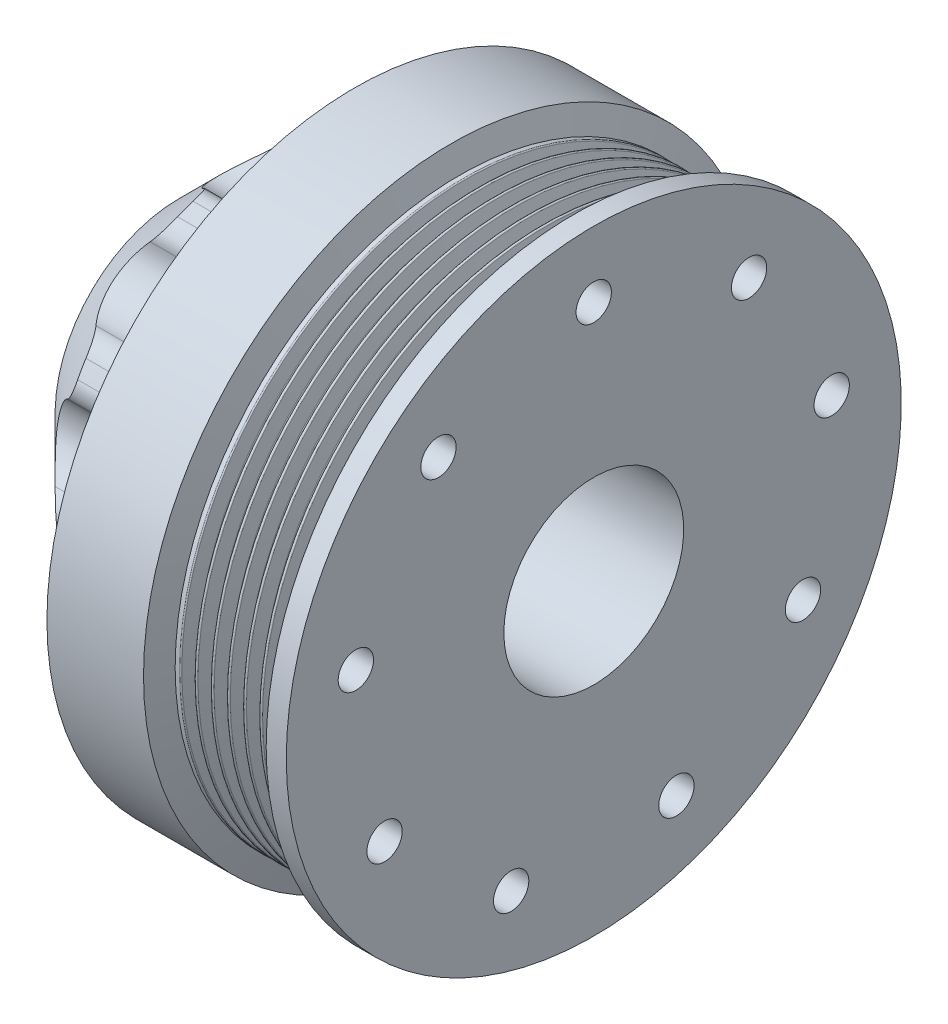
SolidWorks part; units mm, degrees
material "6061-T6 (SS)"
ref_plane "Front Plane" through (0, 0, 0) normal (0, 0, 1) x (1, 0, 0)
ref_plane "Top Plane" through (0, 0, 0) normal (0, 1, 0) x (1, 0, 0)
ref_plane "Right Plane" through (0, 0, 0) normal (1, 0, 0) x (0, 0, -1)
sketch "Sketch1" plane through (0, 0, 0) normal (0, 0, 1) x (1, 0, 0)
  line L0 (0, 0) -> (106.255, 0) construction
  line L1 (-19.05, 13) -> (40.95, 13)
  line L2 (40.95, 13) -> (40.95, 44.45)
  line L3 (40.95, 44.45) -> (6.35, 44.45)
  line L4 (6.35, 44.45) -> (6.35, 28.575)
  line L5 (6.35, 28.575) -> (-19.05, 28.575)
  line L6 (-19.05, 28.575) -> (-19.05, 13)
  line L7 (6.35, 23.3759) -> (6.35, 30.1323) construction
  dimension "D1" = 34.6
  dimension "D2" = 88.9
  dimension "D3" = 26
  dimension "D4" = 25.4
  dimension "D5" = 57.15
revolve "Revolve1" add sketch "Sketch1" angle 360 about L0
sketch "Sketch3" plane through (-19.05, 0, 0) normal (-1, 0, 0) x (0, 0, 1)
  line L0 (0, 0) -> (0, 34.925) construction
  arc A0 (-6.0532, 27.9265) -> (6.0532, 27.9265) centre (0, 29.845) ccw
  circle A1 centre (0, 0) radius 28.575 construction
  arc A2 (6.0532, 27.9265) -> (-6.0532, 27.9265) centre (0, 0) ccw
  point P6 (0, 23.495)
  point P10 (0, 28.575)
  dimension "D1" = 34.925
  dimension "D2" = 5.08
  dimension "D3" = 6.35
extrude "Cut-Extrude1" cut sketch "Sketch3" against normal up to surface (25.4 mm away) up to face at (6.35, 0, 28.575)
fillet "Fillet1" radius 3.175 2 edges at (-6.35, 27.9265, 6.0532) (-6.35, 27.9265, -6.0532)
sketch "Sketch6" plane through (6.35, 0, 0) normal (-1, 0, 0) x (0, 0, 1)
  point P0 (0, 34.925)
hole_wizard "1/4-20 Tapped Hole1" positions "Sketch7" profile "Sketch9" tap size "1/4-20" standard "ANSI Inch" end condition through all
sketch "Sketch7" plane through (6.35, 0, 0) normal (-1, 0, 0) x (0, 0, 1)
  point P0 (0, 34.925)
sketch "Sketch9" plane through (6.35, 34.925, 0) normal (0, 1, 0) x (0, 0, 1)
  line L0 (0, 0) -> (0, 34.6)
  line L1 (0, 34.6) -> (2.5527, 34.6)
  line L2 (2.5527, 34.6) -> (2.5527, 0)
  line L5 (2.5527, 0) -> (0, 0)
  line L11 (0, -6.35) -> (0, 107.95) construction
  dimension "Thru Tap Drill Dia." = 5.1054
  dimension "Thru Tap Drill Depth" = 34.6
pattern_circular "CirPattern1" count 9 over 360 about axis through (6.35, 0, 0) along (-1, 0, 0) of "Cut-Extrude1", "Fillet1", "1/4-20 Tapped Hole1"
sketch "Sketch14" plane through (6.35, 0, 0) normal (-1, 0, 0) x (0, 0, 1)
  line L1 (22.4494, 26.7541) -> (33.8007, 40.2821) construction
  line L2 (0, 34.925) -> (0, 54.7046) construction
  arc A4 (10.6724, 36.5747) -> (15.3343, 34.8779) centre (0, 0) cw
  circle A5 centre (0, 0) radius 44.45 construction
  arc A6 (8.7158, 29.8694) -> (12.523, 28.4836) centre (0, 0) cw
  arc A7 (10.8892, 26.4189) -> (8.6401, 27.2374) centre (0, 0) ccw construction
  arc A8 (12.523, 28.4836) -> (15.3343, 34.8779) centre (13.9286, 31.6808) ccw
  arc A9 (8.7158, 29.8694) -> (10.6724, 36.5747) centre (9.6941, 33.222) cw
  circle A10 centre (22.4494, 26.7541) radius 6.35 construction
  circle A11 centre (0, 34.925) radius 6.35 construction
  point P9 (0, 34.925)
  dimension "D2" = 6.35
  dimension "D4" = 2.54
  dimension "D1" = 12.7
extrude "Cut-Extrude2" [suppressed] cut sketch "Sketch14" against normal offset from surface (25.075 mm away) 9.525 up to face at (40.95, 26.7541, 25.0021)
pattern_circular "CirPattern2" [suppressed] count 9 over 360 of bodies 109
sketch "Sketch10" plane through (0, 0, 0) normal (0, 0, 1) x (1, 0, 0)
  line L0 (40.95, 44.45) -> (6.35, 44.45) construction
  line L2 (35.9966, 40.9635) -> (35.401, 39.3272)
  line L3 (34.6372, 39.3272) -> (34.0416, 40.9635)
  line L9 (36.1875, 44.45) -> (33.8507, 44.45)
  line L10 (40.95, 44.45) -> (6.35, 44.45) construction
  line L11 (34.0416, 40.9635) -> (35.9966, 40.9635) construction
  line L12 (0, 0) -> (72.0631, 0) construction
  line L13 (36.1875, 41.0972) -> (36.1875, 44.45)
  line L14 (33.8507, 41.0972) -> (33.8507, 44.45)
  line L15 (33.2905, 39.0598) -> (37.1262, 39.0598) construction
  line L16 (32.9874, 42.291) -> (37.178, 42.291) construction
  arc A0 (34.6372, 39.3272) -> (35.401, 39.3272) centre (35.0191, 39.4662) ccw
  arc A1 (35.9966, 40.9635) -> (36.1875, 41.0972) centre (36.1875, 40.894) cw
  arc A2 (34.0416, 40.9635) -> (33.8507, 41.0972) centre (33.8507, 40.894) ccw
  point P22 (39.3625, 41.5722)
  point P25 (37.0257, 42.4168)
  dimension "D4" = 4.7625
  dimension "D2" = 40
  dimension "D5" = 2.0374
  dimension "D6" = 2.3368
  dimension "D7" = 42.291
  dimension "D8" = 1.1938
ref_axis "Axis1" through (40.95, 0, 0) along (-1, 0, 0)
revolve "Cut-Revolve1" cut sketch "Sketch10" angle 360 about axis through (40.95, 0, 0) along (-1, 0, 0)
pattern_linear "LPattern2" count 6 spacing 2.3368 along (-1, 0, 0) of "Cut-Revolve1"
sketch "Sketch23" plane through (0, 0, 0) normal (0, 0, 1) x (1, 0, 0)
  line L0 (36.1875, 41.0972) -> (36.8225, 41.0972)
  line L1 (36.8225, 41.0972) -> (38.0428, 44.45)
  line L2 (40.95, 44.45) -> (36.1875, 44.45) construction
  line L3 (38.0428, 44.45) -> (36.1875, 44.45)
  line L4 (36.1875, 44.45) -> (36.1875, 41.0972)
  line L5 (35.0191, 39.0598) -> (35.0191, 41.518) construction
  line L6 (29.1771, 41.0972) -> (29.1771, 44.846) construction
  line L7 (22.1667, 44.45) -> (22.1667, 41.0972)
  line L8 (20.3114, 44.45) -> (22.1667, 44.45)
  line L9 (21.5317, 41.0972) -> (20.3114, 44.45)
  line L10 (22.1667, 41.0972) -> (21.5317, 41.0972)
  line L11 (40.95, 44.45) -> (36.1875, 44.45) construction
  arc A0 (34.6372, 39.3272) -> (35.401, 39.3272) centre (35.0191, 39.4662) ccw construction
  arc A1 (29.368, 40.9635) -> (28.9862, 40.9635) centre (29.1771, 40.894) ccw construction
  point P22 (38.41, 44.45)
  point P25 (39.0105, 44.45)
  dimension "D1" = 1.8034
  dimension "D2" = 20
revolve "Cut-Revolve3" cut sketch "Sketch23" angle 360 about axis through (40.95, 0, 0) along (-1, 0, 0)
sketch "Sketch11" plane through (0, 0, 0) normal (0, 0, 1) x (1, 0, 0)
  line L1 (6.35, 44.45) -> (-19.05, 44.45)
  line L2 (-19.05, 44.45) -> (-19.05, 17.8611)
  line L3 (-19.05, 13) -> (-19.05, -13) construction
  line L4 (0, 0) -> (-37.8551, 0) construction
  line L5 (-19.05, 17.8611) -> (6.35, 43.2611)
  line L6 (6.35, 43.2611) -> (6.35, 44.45)
  line L7 (6.35, 27.3861) -> (-19.05, 27.3861) construction
  dimension "D1" = 9.525
  dimension "D2" = 45
revolve "Cut-Revolve2" cut sketch "Sketch11" angle 360 about L4
equation "\"D7@Sketch10\"=3.33in/2"
equation "\"D8@Sketch10\"=.094/2"
